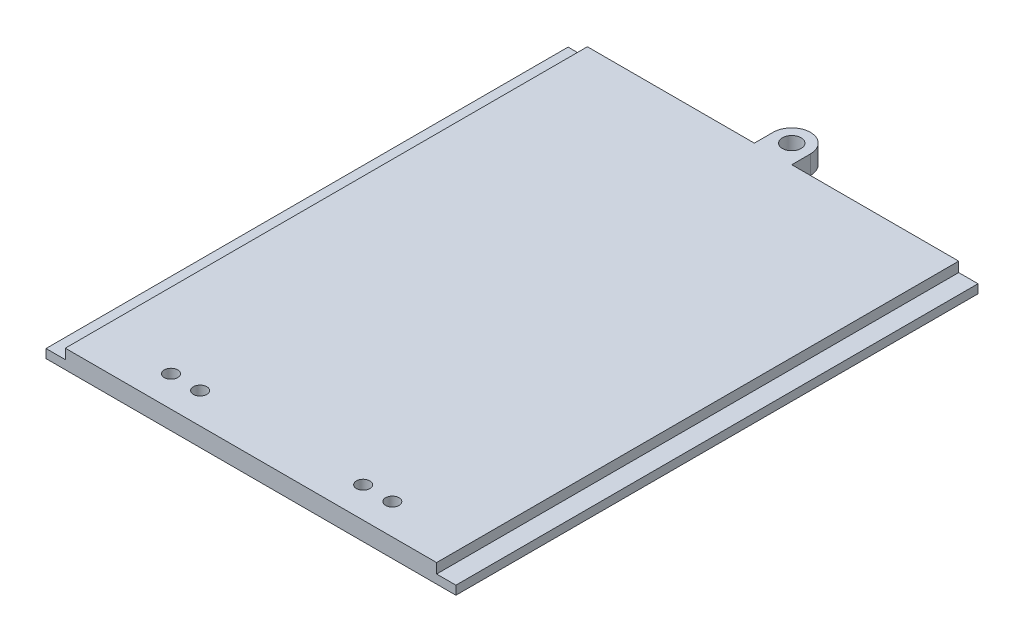
SolidWorks part; units mm, degrees
ref_plane "Front Plane" through (0, 0, 0) normal (0, 0, 1) x (1, 0, 0)
ref_plane "Top Plane" through (0, 0, 0) normal (0, 1, 0) x (1, 0, 0)
ref_plane "Right Plane" through (0, 0, 0) normal (1, 0, 0) x (0, 0, -1)
sketch "Sketch1" plane through (0, 0, 0) normal (0, 1, 0) x (1, 0, 0)
  line L1 (0, 0) -> (139.192, 0)
  line L2 (0, 0) -> (0, 177.292)
  line L3 (0, 177.292) -> (139.192, 177.292)
  line L4 (139.192, 0) -> (139.192, 177.292)
  dimension "D1" = 139.192
  dimension "D2" = 177.292
extrude "Boss-Extrude1" add sketch "Sketch1" along normal blind 6.35
sketch "Sketch2" plane through (0, 6.35, 0) normal (0, 1, 0) x (1, 0, 0)
  line L0 (69.596, 177.292) -> (69.596, 0) construction
  line L1 (139.192, 177.292) -> (0, 177.292) construction
  line L2 (0, 0) -> (139.192, 0) construction
  line L3 (132.642, 177.292) -> (132.642, 0)
  line L4 (0, 177.292) -> (6.55, 177.292)
  line L5 (0, 177.292) -> (0, 0)
  line L6 (0, 0) -> (6.55, 0)
  line L7 (6.55, 177.292) -> (6.55, 0)
  line L8 (139.192, 0) -> (132.642, 0)
  line L9 (139.192, 177.292) -> (139.192, 0)
  line L10 (139.192, 177.292) -> (132.642, 177.292)
  dimension "D1" = 6.55
extrude "Cut-Extrude1" cut sketch "Sketch2" against normal blind 3.375
sketch "Sketch3" plane through (0, 6.35, 0) normal (0, 1, 0) x (1, 0, 0)
  line L0 (132.642, 177.292) -> (6.55, 177.292) construction
  line L1 (63.246, 177.292) -> (75.946, 177.292)
  line L2 (63.246, 177.292) -> (63.246, 189.992)
  line L3 (63.246, 189.992) -> (75.946, 189.992)
  line L4 (75.946, 177.292) -> (75.946, 189.992)
  line L5 (139.192, 177.292) -> (0, 177.292) construction
  point P6 (69.596, 177.292)
  point P9 (69.596, 177.292)
  dimension "D1" = 12.7
  dimension "D2" = 12.7
extrude "Boss-Extrude2" add sketch "Sketch3" against normal blind 6.35
fillet "Fillet1" radius 6.35 2 edges at (63.246, 3.175, -189.992) (75.946, 3.175, -189.992)
sketch "Sketch4" plane through (0, 6.35, 0) normal (0, 1, 0) x (1, 0, 0)
  circle A0 centre (69.596, 183.642) radius 3.175
  dimension "D1" = 6.35
extrude "Cut-Extrude2" cut sketch "Sketch4" against normal through all
sketch "Sketch5" plane through (0, 0, 0) normal (0, -1, 0) x (1, 0, 0)
  line L0 (107.188, -8.128) -> (107.188, 0) construction
  line L1 (0, 0) -> (139.192, 0) construction
  line L2 (109.474, -10.414) -> (139.192, -10.414) construction
  line L3 (139.192, 0) -> (139.192, -177.292) construction
  line L4 (104.902, -10.414) -> (99.568, -10.414) construction
  line L5 (39.624, -10.414) -> (34.29, -10.414) construction
  line L7 (94.996, -10.414) -> (44.196, -10.414) construction
  line L8 (29.718, -10.414) -> (0, -10.414) construction
  line L9 (0, -177.292) -> (0, 0) construction
  circle A0 centre (107.188, -10.414) radius 2.286
  circle A1 centre (97.282, -10.414) radius 2.286
  circle A2 centre (41.91, -10.414) radius 2.286
  circle A3 centre (32.004, -10.414) radius 2.286
  dimension "D2" = 4.572
  dimension "D3" = 4.572
  dimension "D4" = 4.572
  dimension "D5" = 4.572
  dimension "D1" = 8.128
  dimension "D6" = 5.334
  dimension "D7" = 5.334
  dimension "D8" = 50.8
extrude "Cut-Extrude3" cut sketch "Sketch5" against normal blind 12.7
